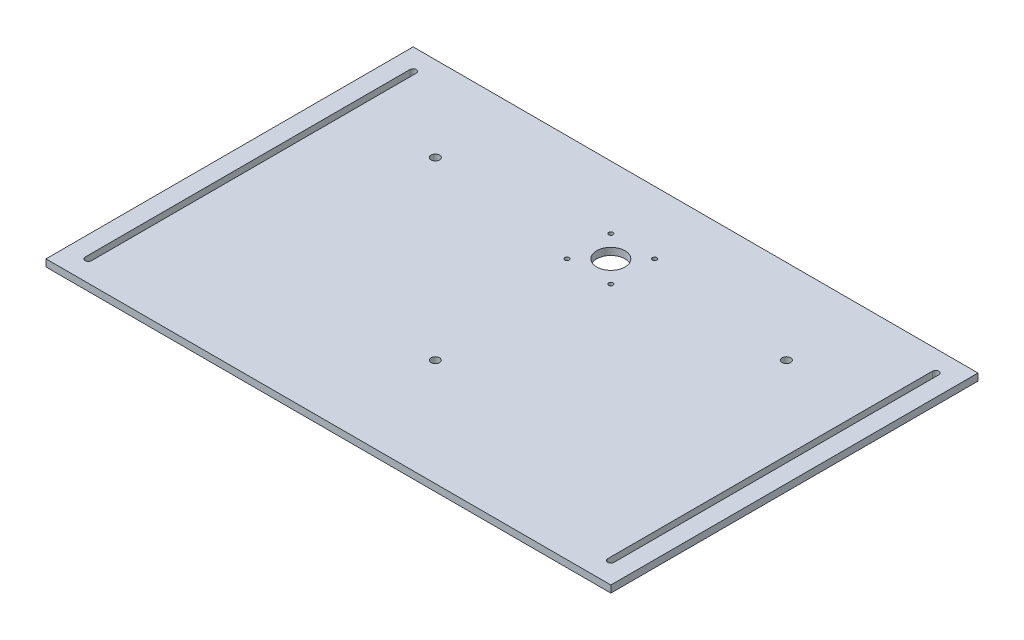
SolidWorks part; units mm, degrees
ref_plane "前基準面" through (0, 0, 0) normal (0, 0, 1) x (1, 0, 0)
ref_plane "上基準面" through (0, 0, 0) normal (0, 1, 0) x (1, 0, 0)
ref_plane "右基準面" through (0, 0, 0) normal (1, 0, 0) x (0, 0, -1)
sketch "草圖1" plane through (0, 0, 0) normal (0, 1, 0) x (1, 0, 0)
  line L0 (200, 60) -> (170, 60) construction
  line L1 (200, 160) -> (-200, 160) construction
  line L2 (200, 160) -> (200, -160) construction
  line L3 (200, -160) -> (-200, -160) construction
  line L4 (-200, 160) -> (-200, -160) construction
  line L5 (0, -160) -> (0, 160) construction
  line L6 (200, 0) -> (-200, 0) construction
  line L7 (-200, 160) -> (200, 160) construction
  line L8 (-200, 160) -> (-200, 130) construction
  line L9 (-200, 130) -> (200, 130) construction
  line L10 (200, 160) -> (200, 130) construction
  line L11 (-200, 130) -> (-170, 130) construction
  line L12 (-200, 130) -> (-200, -130) construction
  line L13 (-200, -130) -> (-170, -130) construction
  line L14 (-170, 130) -> (-170, -130) construction
  line L15 (200, -160) -> (-200, -160) construction
  line L16 (200, -160) -> (200, -130) construction
  line L17 (200, -130) -> (-200, -130) construction
  line L18 (-200, -160) -> (-200, -130) construction
  line L19 (200, -130) -> (170, -130) construction
  line L20 (200, -130) -> (200, 130) construction
  line L21 (200, 130) -> (170, 130) construction
  line L22 (170, -130) -> (170, 130) construction
  line L23 (-200, 130) -> (-170, 130) construction
  line L24 (-200, 130) -> (-200, 60) construction
  line L25 (-200, 60) -> (-170, 60) construction
  line L26 (-170, 130) -> (-170, 60) construction
  line L27 (170, 130) -> (170, 60) construction
  line L29 (200, 130) -> (200, 60) construction
  line L30 (-200, -60) -> (-170, -60) construction
  line L31 (-170, -130) -> (-170, -60) construction
  line L32 (-200, -130) -> (-170, -130) construction
  line L33 (-200, -130) -> (-200, -60) construction
  line L34 (200, -130) -> (200, -60) construction
  line L35 (170, -130) -> (170, -60) construction
  line L36 (200, -60) -> (170, -60) construction
  line L37 (200, -130) -> (170, -130) construction
  line L40 (-200, 130) -> (-200, -130)
  line L42 (200, 130) -> (200, -130)
  line L43 (-200, 130) -> (200, 130)
  line L44 (-200, 130) -> (-200, -130)
  line L45 (-200, -130) -> (200, -130)
  line L46 (200, 130) -> (200, -130)
  point P0 (0, 0)
  dimension "D1" = 400
  dimension "D2" = 320
  dimension "D4" = 30
  dimension "D6" = 30
  dimension "D7" = 70
extrude "填料-伸長1" add sketch "草圖1" along normal blind 5 contours L40 L45 L42 L43 region at (0, 0, 0)
sketch "草圖2" plane through (0, 5, 0) normal (0, 1, 0) x (1, 0, 0)
  line L0 (-185, 130) -> (-185, -130) construction
  line L1 (-200, 130) -> (200, 130) construction
  line L2 (-200, -130) -> (200, -130) construction
  line L3 (185, -130) -> (185, 130) construction
  line L4 (-185, 115) -> (-185, -115) construction
  line L5 (-182.75, 115) -> (-182.75, -115)
  line L6 (-187.25, 115) -> (-187.25, -115)
  line L7 (-200, 60) -> (-170, 60) construction
  line L8 (200, 0) -> (-200, 0) construction
  line L9 (0, -160) -> (0, 160) construction
  line L10 (0, -160) -> (0, 160) construction
  line L11 (185, 115) -> (185, -115) construction
  line L12 (182.75, 115) -> (182.75, -115)
  line L13 (187.25, 115) -> (187.25, -115)
  arc A0 (-182.75, 115) -> (-187.25, 115) centre (-185, 115) ccw
  arc A1 (-187.25, -115) -> (-182.75, -115) centre (-185, -115) ccw
  arc A2 (182.75, 115) -> (187.25, 115) centre (185, 115) cw
  arc A3 (187.25, -115) -> (182.75, -115) centre (185, -115) cw
  point P10 (-185, 0)
  point P17 (-185, 60)
  point P25 (185, 0)
  dimension "D1" = 4.5
  dimension "D2" = 230
extrude "除料-伸長1" cut sketch "草圖2" against normal through all
sketch "草圖3" plane through (0, 5, 0) normal (0, 1, 0) x (1, 0, 0)
  line L0 (0, -160) -> (0, 160) construction
  line L5 (-200, 130) -> (-200, -130) construction
  line L10 (-200, 190) -> (200, 190) construction
  line L11 (-200, 190) -> (-200, 130) construction
  line L12 (-200, 130) -> (200, 130) construction
  line L13 (-21.15, 85.5) -> (-15.5, 91.15) construction
  line L14 (-15.5, 91.15) -> (15.5, 91.15) construction
  line L15 (-21.15, 85.5) -> (-21.15, 54.5) construction
  line L16 (-15.5, 48.85) -> (15.5, 48.85) construction
  line L17 (21.15, 85.5) -> (21.15, 54.5) construction
  line L18 (15.5, 91.15) -> (21.15, 85.5) construction
  line L19 (15.5, 48.85) -> (21.15, 54.5) construction
  line L20 (-21.15, 54.5) -> (-15.5, 48.85) construction
  line L21 (200, 190) -> (200, 130) construction
  line L22 (-127.3048, 73) -> (-121.3048, 73) construction
  line L23 (-121.3048, 73) -> (-121.3048, 67) construction
  line L24 (-121.3048, 67) -> (-127.3048, 67) construction
  line L25 (-3, -57.3048) -> (-3, -51.3048) construction
  line L26 (-3, -51.3048) -> (3, -51.3048) construction
  line L27 (3, -51.3048) -> (3, -57.3048) construction
  line L28 (127.3048, 67) -> (121.3048, 67) construction
  line L29 (121.3048, 67) -> (121.3048, 73) construction
  line L30 (121.3048, 73) -> (127.3048, 73) construction
  line L31 (3, 197.3048) -> (3, 191.3048) construction
  line L32 (3, 191.3048) -> (-3, 191.3048) construction
  line L33 (-3, 191.3048) -> (-3, 197.3048) construction
  line L34 (-121.3048, 70) -> (121.3048, 70) construction
  line L35 (0, -51.3048) -> (0, 191.3048) construction
  circle A4 centre (-15.5, 85.5) radius 1.55
  circle A5 centre (15.5, 85.5) radius 1.55
  circle A6 centre (-15.5, 54.5) radius 1.55
  circle A7 centre (15.5, 54.5) radius 1.55
  circle A8 centre (0, 70) radius 10
  arc A9 (-3, 197.3048) -> (-127.3048, 73) centre (2, 68) ccw construction
  arc A10 (-127.3048, 67) -> (-3, -57.3048) centre (2, 72) ccw construction
  arc A11 (3, -57.3048) -> (127.3048, 67) centre (-2, 72) ccw construction
  arc A12 (127.3048, 73) -> (3, 197.3048) centre (-2, 68) ccw construction
  circle A13 centre (-124.3048, 70) radius 3
  circle A14 centre (124.3048, 70) radius 3
  circle A15 centre (0, -54.3048) radius 3
  point P0 (0, 70)
  point P32 (0, 91.15)
  point P50 (-21.15, 70)
  point P51 (0, 70)
  dimension "D2" = 42.3
  dimension "D10" = 45
  dimension "D5" = 3.1
  dimension "D11" = 20
  dimension "D12" = 129.4014
  dimension "D17" = 6
  dimension "D18" = 6
  dimension "D1" = 42.3
  dimension "D3" = 31
  dimension "D4" = 31
  dimension "D7" = 5.65
  dimension "D8" = 60
  dimension "D9" = 60
  dimension "D16" = 4
  dimension "D6" = 5.65
  dimension "D13" = 6
  dimension "D14" = 6
  dimension "D15" = 4
extrude "除料-伸長2" cut sketch "草圖3" against normal through all
